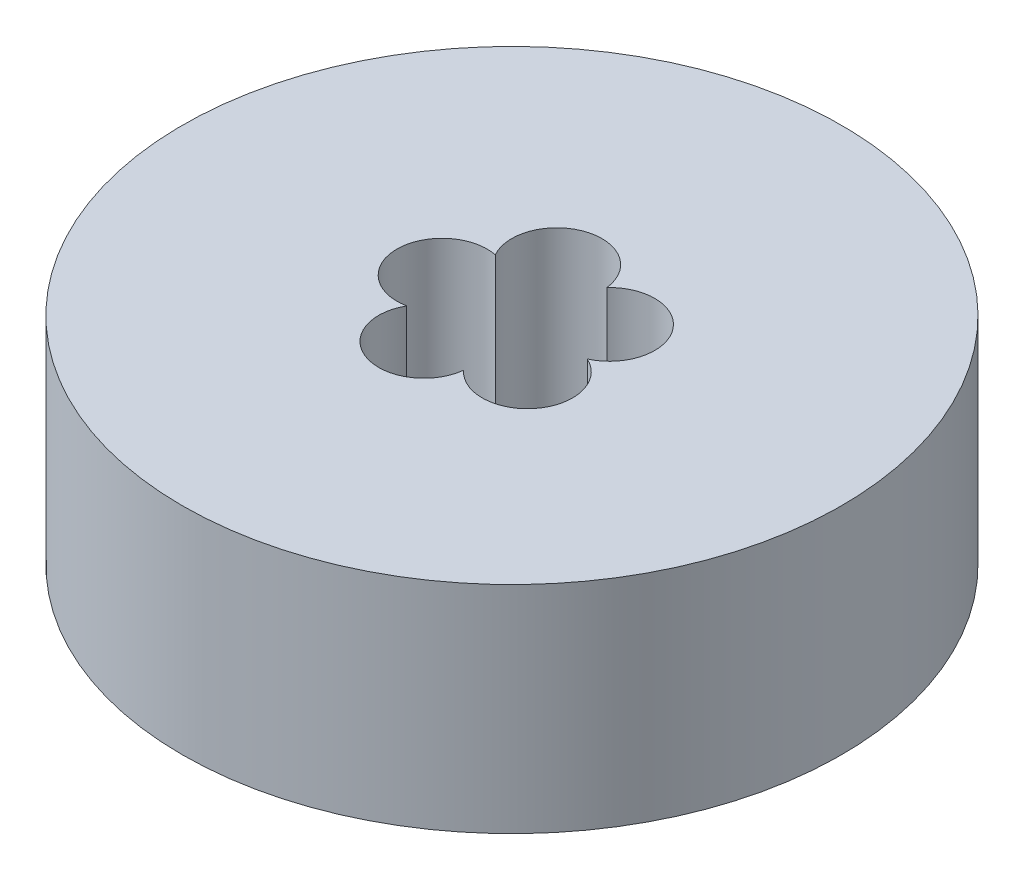
SolidWorks part; units mm, degrees
ref_plane "Front Plane" through (0, 0, 0) normal (0, 0, 1) x (1, 0, 0)
ref_plane "Top Plane" through (0, 0, 0) normal (0, 1, 0) x (1, 0, 0)
ref_plane "Right Plane" through (0, 0, 0) normal (1, 0, 0) x (0, 0, -1)
sketch "Sketch1" plane through (0, 0, 0) normal (0, 1, 0) x (1, 0, 0)
  circle A0 centre (0, 0) radius 27.5
  dimension "FLANGE_OD" = 55
extrude "Boss-Extrude1" add sketch "Sketch1" along normal blind 18
sketch "Sketch2" plane through (0, 0, 0) normal (0, 1, 0) x (1, 0, 0)
  circle A0 centre (0, 0) radius 5
  dimension "BORE_D" = 10
extrude "Cut-Extrude1" cut sketch "Sketch2" along normal through all
sketch "Sketch3" plane through (0, 18, 0) normal (0, 1, 0) x (1, 0, 0)
  circle A0 centre (0, 0) radius 5.8327 construction
  circle A1 centre (-5.8327, 0) radius 3.7696
  dimension "BOLT_D" = 7.5392
  dimension "BOLT_PCD" = 11.6655
extrude "Cut-Extrude2" cut sketch "Sketch3" against normal blind 15.2588
pattern_circular "CirPattern1" count 5 over 360 about axis through (0, 0, 0) along (0, 1, 0) of "Cut-Extrude2"
